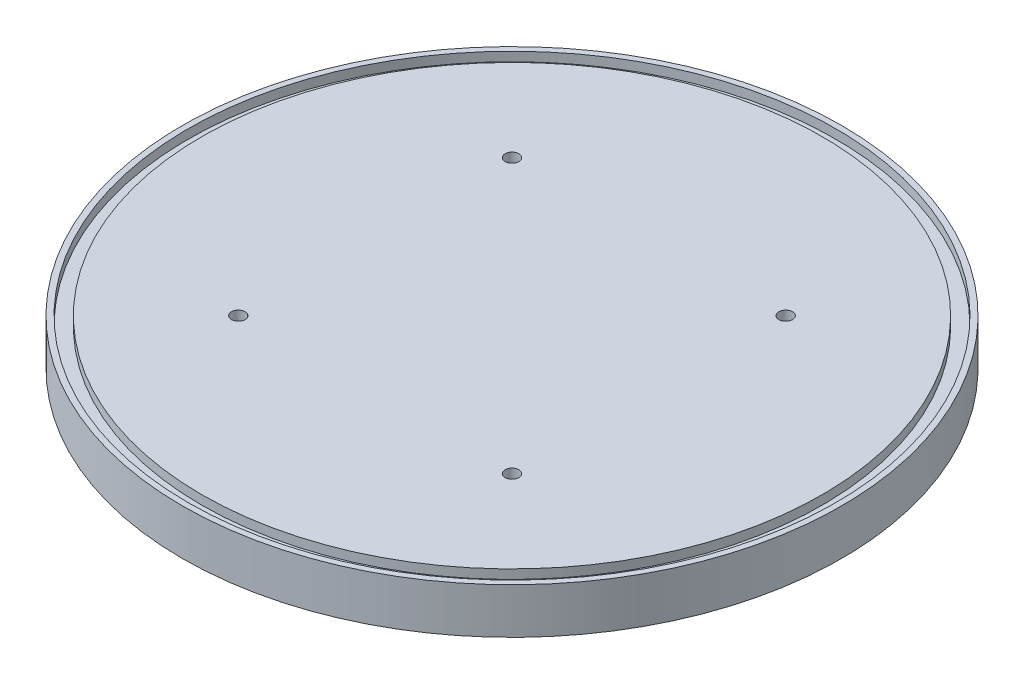
SolidWorks part; units mm, degrees
ref_plane "前基準面" through (0, 0, 0) normal (0, 0, 1) x (1, 0, 0)
ref_plane "上基準面" through (0, 0, 0) normal (0, 1, 0) x (1, 0, 0)
ref_plane "右基準面" through (0, 0, 0) normal (1, 0, 0) x (0, 0, -1)
sketch "草圖1" plane through (0, 0, 0) normal (0, 1, 0) x (1, 0, 0)
  line L0 (0, 78.355) -> (0, -92.3476) construction
  line L1 (-97.6496, 0) -> (95.3358, 0) construction
  line L2 (-62.1665, 11) -> (-62.1665, -11) construction
  line L3 (-34, 34) -> (34, 34) construction
  line L4 (-34, 34) -> (-34, -34) construction
  line L5 (-34, -34) -> (34, -34) construction
  line L6 (34, 34) -> (34, -34) construction
  line L7 (-34, 34) -> (34, -34) construction
  line L8 (-34, -34) -> (34, 34) construction
  line L9 (-62.1665, 11) -> (-72.1665, 11) construction
  line L10 (-62.1665, -11) -> (-72.1665, -11) construction
  line L11 (-62.1665, 11) -> (-47.1665, 11) construction
  line L12 (-47.1665, 11) -> (-47.1665, -11) construction
  line L13 (-47.1665, -11) -> (-62.1665, -11) construction
  circle A0 centre (0, 0) radius 72.25
  circle A1 centre (0, 0) radius 71
  circle A2 centre (0, 0) radius 68
  circle A4 centre (0, 0) radius 73 construction
  circle A5 centre (0, 0) radius 66
  point P7 (0, 0)
  point P12 (-30, 30)
  point P14 (30, 30)
  point P17 (30, -30)
  point P18 (-30, -30)
  point P19 (0, 0)
  point P23 (-73, 0)
  point P25 (-62.1665, 0)
  dimension "D1" = 144.5
  dimension "D5" = 142
  dimension "D6" = 3
  dimension "D7" = 2
  dimension "D8" = 146
  dimension "D9" = 10
  dimension "D2" = 68
  dimension "D3" = 4
  dimension "D10" = 22
  dimension "D11" = 15
  dimension "D4" = 4
extrude "填料-伸長7" add sketch "草圖1" along normal blind 10 contours A0
hole_wizard "Ø3.0mm 定位孔1" positions "草圖8" profile "草圖9" hole size "Ø3.0" standard "ISO"
sketch "草圖8" plane through (0, 10, 0) normal (0, 1, 0) x (1, 0, 0)
  point P0 (-30, 30)
  point P5 (-30, -30)
  point P8 (30, -30)
  point P10 (30, 30)
sketch "草圖9" plane through (-30, 10, -30) normal (1, 0, 0) x (0, 0, 1)
  line L0 (0, 0) -> (0, 6.9013)
  line L1 (0, 6.9013) -> (1.5, 6)
  line L2 (1.5, 6) -> (1.5, 0)
  line L5 (1.5, 0) -> (0, 0)
  line L10 (0, 6.9013) -> (-1.5, 6) construction
  line L11 (0, -6.35) -> (0, 107.95) construction
  dimension "鑽孔直徑" = 3
  dimension "鑽孔深度" = 6
  dimension "導頭角度" = 118
extrude "除料-伸長1" cut sketch "草圖1<11>" against normal blind 2 from surface contours A1 A2 region at (-68.9918, 0, 0) starting at face at (-30, 10, -28.5)
sketch "草圖1<11>" plane through (0, 0, 0) normal (0, 1, 0) x (1, 0, 0) same geometry as "草圖1"
